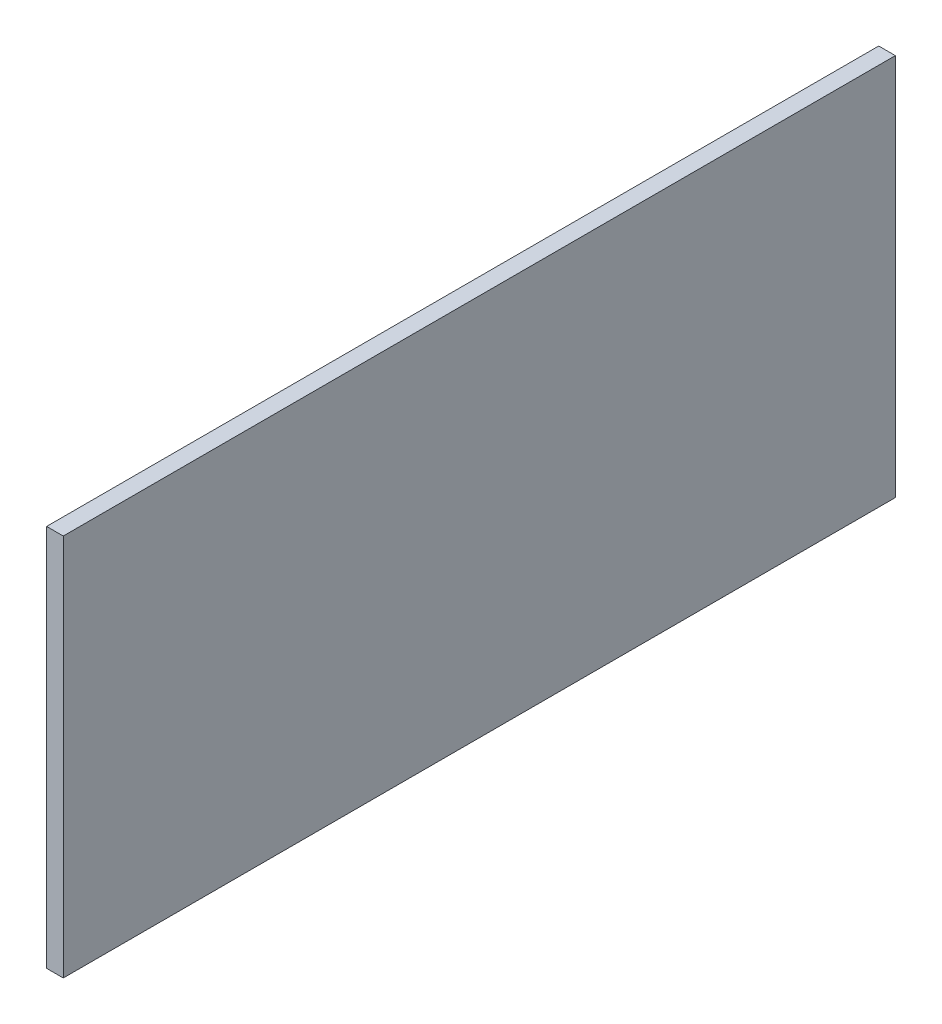
SolidWorks part; units mm, degrees
material "6061-T4 (SS)"
ref_plane "Front Plane" through (0, 0, 0) normal (0, 0, 1) x (1, 0, 0)
ref_plane "Top Plane" through (0, 0, 0) normal (0, 1, 0) x (1, 0, 0)
ref_plane "Right Plane" through (0, 0, 0) normal (1, 0, 0) x (0, 0, -1)
sketch "Sketch1" plane through (0, 0, 0) normal (1, 0, 0) x (0, 0, -1)
  line L1 (0, 0) -> (100, 0)
  line L2 (0, 0) -> (0, 46)
  line L3 (0, 46) -> (100, 46)
  line L4 (100, 0) -> (100, 46)
  dimension "D1" = 46
  dimension "D2" = 100
extrude "Boss-Extrude1" add sketch "Sketch1" along normal blind 2
